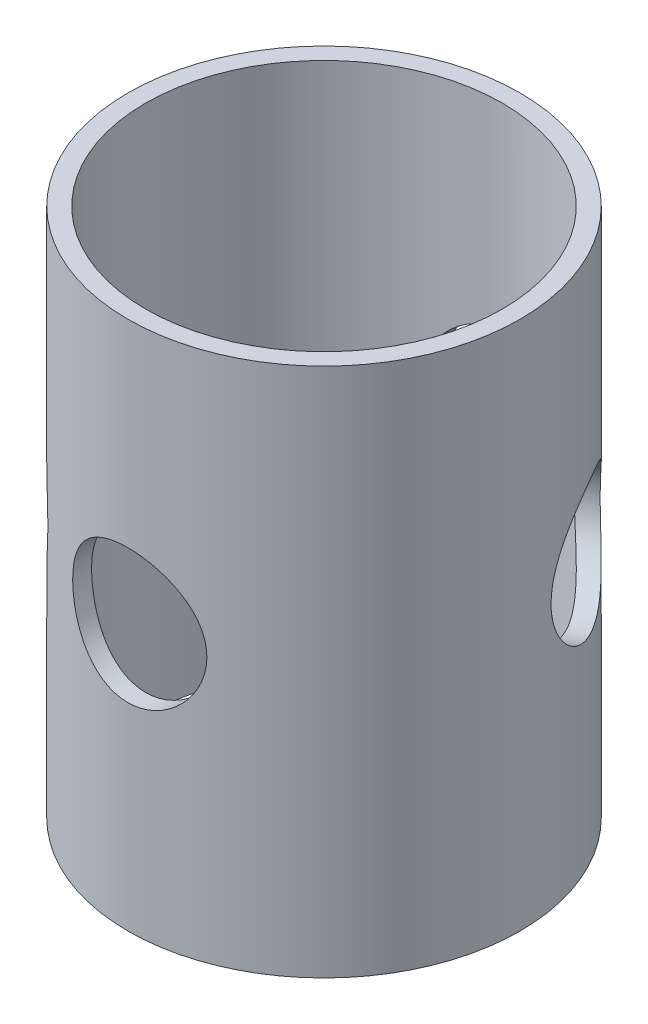
SolidWorks part; units mm, degrees
note: '?' marks a value the reader was unsure of.
ref_plane "Front Plane" through (0, 0, 0) normal (0, 0, 1) x (1, 0, 0)
ref_plane "Top Plane" through (0, 0, 0) normal (0, 1, 0) x (1, 0, 0)
ref_plane "Right Plane" through (0, 0, 0) normal (1, 0, 0) x (0, 0, -1)
sketch "Sketch2" plane through (0, 0, 0) normal (0, 1, 0) x (1, 0, 0)
  circle A0 centre (0, 0) radius 25.654
  circle A1 centre (0, 0) radius 28.194
  dimension "D1" = 25.654
  dimension "D2" = 2.54
extrude "Boss-Extrude1" add sketch "Sketch2" along normal blind 76.2
ref_axis "Axis1" through (0, 76.2, 0) along (0, -1, 0)?
ref_plane "Plane1" through (0, 0, 0) normal (0, 0, 1) x (1, 0, 0)
sketch "Sketch3" plane through (0, 0, 0) normal (0, 0, 1) x (1, 0, 0)
  line L0 (0, 0) -> (0, 38.1)
  line L1 (0, 76.2) -> (0, 0) construction
  circle A0 centre (0, 38.1) radius 9.652
  dimension "D2" = 9.652
  dimension "D1" = 38.1
extrude "Cut-Extrude1" cut sketch "Sketch3" against normal blind 76.2 contours A0
pattern_circular "CirPattern1" count 2 every 60 about axis through (0, 76.2, 0) along (0, -1, 0) of "Cut-Extrude1"
pattern_circular "CirPattern2" count 2 every 180 about axis through (0, 38.1, 0) along (0, 0, 1) of "Cut-Extrude1"
pattern_circular "CirPattern3" count 2 every 120 about axis through (0, 76.2, 0) along (0, -1, 0) of "Cut-Extrude1"
